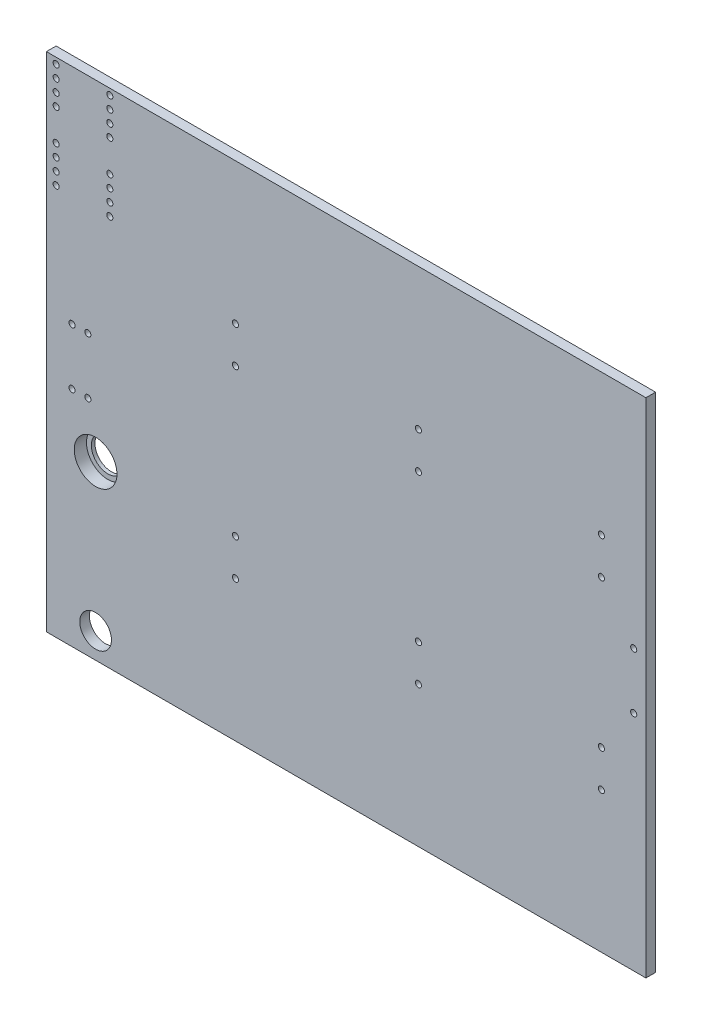
SolidWorks part; units mm, degrees
ref_plane "Alzado" through (0, 0, 0) normal (0, 0, 1) x (1, 0, 0)
ref_plane "Planta" through (0, 0, 0) normal (0, 1, 0) x (1, 0, 0)
ref_plane "Vista lateral" through (0, 0, 0) normal (1, 0, 0) x (0, 0, -1)
sketch "Croquis1" plane through (0, 0, 0) normal (0, 0, 1) x (1, 0, 0)
  line L0 (0, 235) -> (200, 235) construction
  line L1 (0, 380) -> (200, 380)
  line L2 (0, 380) -> (0, 0)
  line L3 (0, 0) -> (200, 0)
  line L4 (200, 380) -> (200, 0)
  line L6 (159.0589, 38.35) -> (40.336, 20.8892) construction
  line L7 (40.336, 20.8892) -> (40.336, 140.8892) construction
  line L8 (40.336, 140.8892) -> (159.0589, 38.35) construction
  line L10 (0, 190) -> (200, 190) construction
  circle A0 centre (40.336, 20.8892) radius 13
  circle A1 centre (40.336, 140.8892) radius 17.5
  dimension "D9" = 169.1108
  dimension "D10" = 26
  dimension "D11" = 35
  dimension "D1" = 380
  dimension "D2" = 145
  dimension "D3" = 200
  dimension "D4" = 45
  dimension "D5" = 40.336
  dimension "D6" = 118.7229
  dimension "D7" = 17.4608
  dimension "D8" = 49.1108
extrude "Saliente-Extruir1" add sketch "Croquis1" along normal blind 7.9375
sketch "Croquis2" plane through (0, 0, 0) normal (0, 0, -1) x (-1, 0, 0)
  line L0 (0, 0) -> (-200, 0) construction
  line L1 (-200, 380) -> (-400, 380)
  line L2 (-200, 380) -> (-200, 0)
  line L3 (-200, 0) -> (-400, 0)
  line L4 (-400, 380) -> (-400, 0)
  dimension "D1" = 200
extrude "Saliente-Extruir2" add sketch "Croquis2" against normal up to surface (7.9375 mm away) up to face at (57.836, 140.8892, 7.9375)
sketch "Croquis3" plane through (0, 0, 0) normal (0, 0, -1) x (-1, 0, 0)
  line L1 (0, 380) -> (-400, 380)
  line L2 (0, 380) -> (0, 412)
  line L3 (0, 412) -> (-400, 412)
  line L4 (-400, 380) -> (-400, 412)
  dimension "D1" = 32
extrude "Saliente-Extruir3" add sketch "Croquis3" against normal up to vertex (7.9375 mm away) up to point (0, 380, 7.9375)
sketch "Croquis4" plane through (0, 0, 0) normal (0, 0, -1) x (-1, 0, 0)
  circle A0 centre (-40.336, 140.8892) radius 25
  circle A1 centre (-40.336, 140.8892) radius 17.5 construction
  circle A2 centre (-40.336, 140.8892) radius 17.5
  dimension "D1" = 50
extrude "Saliente-Extruir4" add sketch "Croquis4" along normal blind 5
ref_plane "Plano1" through (0, 123.3892, 0) normal (0, 1, 0) x (1, 0, 0)
ref_plane "Plano2" through (0, 0, -2.0625) normal (0, 0, 1) x (1, 0, 0)
sketch "Croquis5" plane through (0, 0, -2.0625) normal (0, 0, 1) x (1, 0, 0)
  circle A0 centre (40.336, 140.8892) radius 13.5
  circle A1 centre (40.336, 140.8892) radius 17.5 construction
  circle A2 centre (40.336, 140.8892) radius 17.5
  dimension "D1" = 27
extrude "Saliente-Extruir5" add sketch "Croquis5" against normal up to surface (2.9375 mm away) up to face at (15.336, 140.8892, -5)
sketch "Croquis6" plane through (0, 0, 7.9375) normal (0, 0, 1) x (1, 0, 0)
  line L0 (0, 412) -> (400, 412) construction
  line L1 (400, 0) -> (491.5, 0)
  line L2 (400, 0) -> (400, 412)
  line L3 (400, 412) -> (491.5, 412)
  line L4 (491.5, 0) -> (491.5, 412)
  dimension "D1" = 91.5
extrude "Saliente-Extruir6" add sketch "Croquis6" along direction (0, 0, 1) on the side against the normal up to vertex up to point (400, 0, 0)
sketch "Croquis10" plane through (0, 0, 7.9375) normal (0, 0, 1) x (1, 0, 0)
  point P0 (21, 229)
  point P1 (34, 229)
  point P3 (21, 183)
  point P5 (34, 183)
  point P7 (481.5, 229)
  point P9 (481.5, 183)
hole_wizard "Taladro roscado M6x1.01" positions "Croquis11" profile "Croquis12" tap size "M6x1.0" standard "Ansi Metric" end condition up to next
sketch "Croquis11" plane through (0, 0, 7.9375) normal (0, 0, 1) x (1, 0, 0)
  point P0 (21, 229)
  point P3 (34, 229)
  point P6 (34, 183)
  point P9 (21, 183)
  point P12 (481.5, 229)
  point P15 (481.5, 183)
sketch "Croquis12" plane through (21, 229, 7.9375) normal (1, 0, 0) x (0, -1, 0)
  line L0 (0, 0) -> (0, 7.9375)
  line L1 (0, 7.9375) -> (2.5, 7.9375)
  line L2 (2.5, 7.9375) -> (2.5, 0)
  line L5 (2.5, 0) -> (0, 0)
  line L11 (0, -6.35) -> (0, 107.95) construction
  dimension "Diámetro de perforador para roscar hasta el siguiente" = 5
  dimension "Profundidad de perforador para roscar hasta el siguiente" = 7.9375
cosmetic thread "Rosca de taladro13" parameters "D2"=6
cosmetic thread "Rosca de taladro14" parameters "D2"=6
cosmetic thread "Rosca de taladro15" parameters "D2"=6
cosmetic thread "Rosca de taladro16" parameters "D2"=6
cosmetic thread "Rosca de taladro18" parameters "D2"=6
cosmetic thread "Rosca de taladro37" parameters "D2"=6
sketch "Croquis13" plane through (0, 0, 7.9375) normal (0, 0, 1) x (1, 0, 0)
  line L0 (0, 412) -> (491.5, 412) construction
  line L1 (0, 412) -> (0, 0) construction
  point P0 (8, 407)
  point P1 (52, 407)
  point P2 (8, 397)
  point P3 (52, 397)
  point P4 (8, 387)
  point P5 (52, 387)
  point P6 (8, 377)
  point P7 (52, 377)
  point P8 (52, 351)
  point P9 (52, 341)
  point P10 (8, 341)
  point P11 (8, 331)
  point P12 (52, 331)
  point P13 (52, 321)
  point P16 (8, 321)
  point P19 (8, 351)
  dimension "D1" = 5
  dimension "D2" = 10
  dimension "D3" = 10
  dimension "D4" = 10
  dimension "D5" = 44
  dimension "D6" = 8
  dimension "D7" = 10
  dimension "D8" = 10
  dimension "D9" = 10
  dimension "D10" = 56
hole_wizard "Taladro roscado M6x1.02" positions "Croquis14" profile "Croquis15" tap size "M6x1.0" standard "Ansi Metric" end condition up to next
sketch "Croquis14" plane through (0, 0, 7.9375) normal (0, 0, 1) x (1, 0, 0)
  point P0 (8, 407)
  point P3 (8, 397)
  point P6 (8, 387)
  point P9 (8, 377)
  point P12 (52, 407)
  point P15 (52, 397)
  point P18 (52, 387)
  point P21 (52, 377)
  point P24 (52, 351)
  point P27 (52, 341)
  point P30 (52, 331)
  point P33 (52, 321)
  point P36 (8, 351)
  point P39 (8, 341)
  point P42 (8, 331)
  point P45 (8, 321)
sketch "Croquis15" plane through (8, 407, 7.9375) normal (1, 0, 0) x (0, -1, 0)
  line L0 (0, 0) -> (0, 7.9375)
  line L1 (0, 7.9375) -> (2.5, 7.9375)
  line L2 (2.5, 7.9375) -> (2.5, 0)
  line L5 (2.5, 0) -> (0, 0)
  line L11 (0, -6.35) -> (0, 107.95) construction
  dimension "Diámetro de perforador para roscar hasta el siguiente" = 5
  dimension "Profundidad de perforador para roscar hasta el siguiente" = 7.9375
cosmetic thread "Rosca de taladro19" parameters "D2"=6
cosmetic thread "Rosca de taladro20" parameters "D2"=6
cosmetic thread "Rosca de taladro21" parameters "D2"=6
cosmetic thread "Rosca de taladro22" parameters "D2"=6
cosmetic thread "Rosca de taladro23" parameters "D2"=6
cosmetic thread "Rosca de taladro24" parameters "D2"=6
cosmetic thread "Rosca de taladro25" parameters "D2"=6
cosmetic thread "Rosca de taladro26" parameters "D2"=6
cosmetic thread "Rosca de taladro27" parameters "D2"=6
cosmetic thread "Rosca de taladro28" parameters "D2"=6
cosmetic thread "Rosca de taladro29" parameters "D2"=6
cosmetic thread "Rosca de taladro30" parameters "D2"=6
cosmetic thread "Rosca de taladro31" parameters "D2"=6
cosmetic thread "Rosca de taladro32" parameters "D2"=6
cosmetic thread "Rosca de taladro33" parameters "D2"=6
cosmetic thread "Rosca de taladro34" parameters "D2"=6
sketch "Croquis16" plane through (0, 0, 7.9375) normal (0, 0, 1) x (1, 0, 0)
  line L1 (491.5, 0) -> (491.5, 412) construction
  line L2 (0, 412) -> (491.5, 412) construction
  point P0 (455, 296.34)
  point P1 (455, 266.34)
  point P2 (305, 296.34)
  point P3 (155, 266.34)
  point P4 (305, 266.34)
  point P5 (155, 296.34)
  point P6 (155, 145.44)
  point P7 (155, 115.44)
  point P8 (305, 145.44)
  point P9 (305, 115.44)
  point P10 (455, 145.44)
  point P11 (455, 115.44)
  dimension "D1" = 30
  dimension "D2" = 120.9
  dimension "D3" = 30
  dimension "D4" = 36.5
  dimension "D5" = 150
  dimension "D6" = 150
  dimension "D7" = 115.66
hole_wizard "Taladro roscado M6x1.03" positions "Croquis17" profile "Croquis18" tap size "M6x1.0" standard "Ansi Metric" end condition up to next
sketch "Croquis17" plane through (0, 0, 7.9375) normal (0, 0, 1) x (1, 0, 0)
  point P0 (455, 296.34)
  point P3 (455, 266.34)
  point P6 (305, 296.34)
  point P9 (305, 266.34)
  point P12 (155, 296.34)
  point P15 (155, 266.34)
  point P18 (455, 145.44)
  point P21 (455, 115.44)
  point P24 (305, 145.44)
  point P27 (305, 115.44)
  point P30 (155, 145.44)
  point P33 (155, 115.44)
sketch "Croquis18" plane through (455, 296.34, 7.9375) normal (1, 0, 0) x (0, -1, 0)
  line L0 (0, 0) -> (0, 7.9375)
  line L1 (0, 7.9375) -> (2.5, 7.9375)
  line L2 (2.5, 7.9375) -> (2.5, 0)
  line L5 (2.5, 0) -> (0, 0)
  line L11 (0, -6.35) -> (0, 107.95) construction
  dimension "Diámetro de perforador para roscar hasta el siguiente" = 5
  dimension "Profundidad de perforador para roscar hasta el siguiente" = 7.9375
cosmetic thread "Rosca de taladro38" parameters "D2"=6
cosmetic thread "Rosca de taladro39" parameters "D2"=6
cosmetic thread "Rosca de taladro40" parameters "D2"=6
cosmetic thread "Rosca de taladro41" parameters "D2"=6
cosmetic thread "Rosca de taladro42" parameters "D2"=6
cosmetic thread "Rosca de taladro43" parameters "D2"=6
cosmetic thread "Rosca de taladro44" parameters "D2"=6
cosmetic thread "Rosca de taladro45" parameters "D2"=6
cosmetic thread "Rosca de taladro46" parameters "D2"=6
cosmetic thread "Rosca de taladro47" parameters "D2"=6
cosmetic thread "Rosca de taladro48" parameters "D2"=6
cosmetic thread "Rosca de taladro49" parameters "D2"=6
